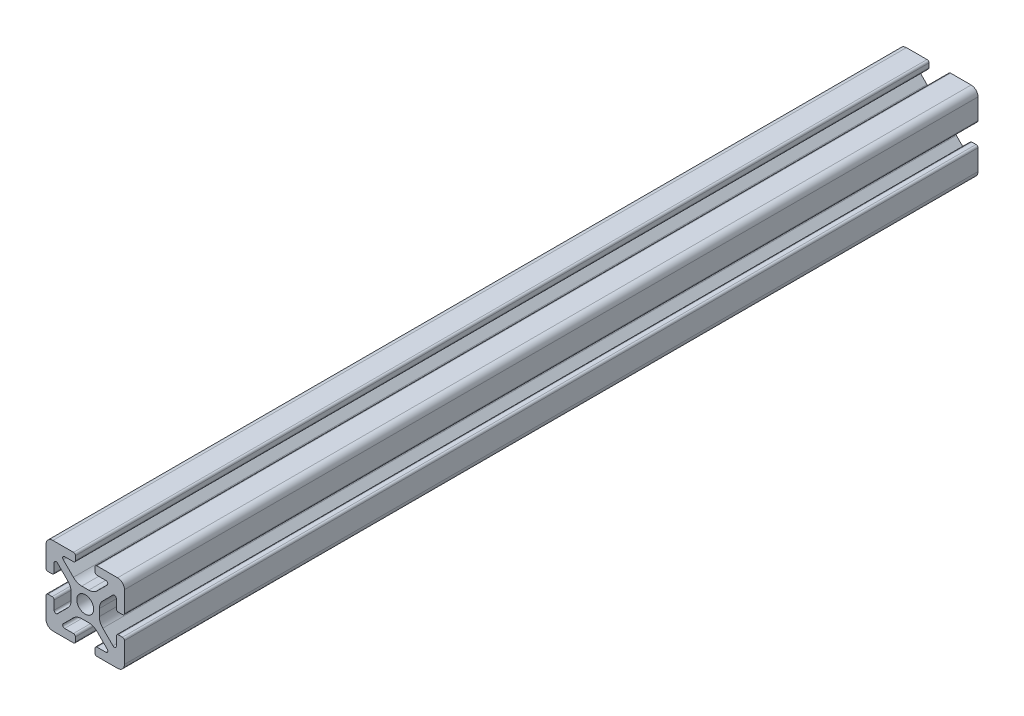
SolidWorks part; units mm, degrees
material "1060 Alloy"
ref_plane "Front Plane" through (0, 0, 0) normal (0, 0, 1) x (1, 0, 0)
ref_plane "Top Plane" through (0, 0, 0) normal (0, 1, 0) x (1, 0, 0)
ref_plane "Right Plane" through (0, 0, 0) normal (1, 0, 0) x (0, 0, -1)
sketch "Sketch2" plane through (0, 0, 0) normal (0, 0, 1) x (1, 0, 0)
  line L0 (0, 10) -> (0, -10) construction
  line L1 (-10, 0) -> (10, 0) construction
  line L2 (2.5, -10) -> (10, -10)
  line L3 (10, -10) -> (10, -2.5)
  line L4 (2.5, -10) -> (2.5, -7.9246)
  line L5 (2.5, -7.9246) -> (6.4571, -7.9246)
  line L6 (6.4571, -7.9246) -> (2.1325, -3.6)
  line L7 (0, 0) -> (10, -10) construction
  line L8 (10, -2.5) -> (7.9246, -2.5)
  line L9 (7.9246, -2.5) -> (7.9246, -6.4571)
  line L10 (7.9246, -6.4571) -> (3.6, -2.1325)
  line L11 (5.7623, -4.2948) -> (4.2948, -5.7623) construction
  circle A0 centre (0, 0) radius 2.15
  arc A1 (5.25, -7.9246) -> (5.6036, -7.0711) centre (5.25, -7.4246) ccw construction
  point P8 (0, -3.6)
  point P16 (5.0286, -5.0286)
  dimension "Center Hole Diameter" = 4.3
  dimension "D3" = 0.5
  dimension "Rail Height" = 20
  dimension "Rail Width" = 20
  dimension "T-Slot Width" = 5
  dimension "Slot Depth" = 6.4
  dimension "Slot Inner Width" = 11.5
sketch "Sketch3" plane through (0, 0, 0) normal (1, 0, 0) x (0, 0, -1)
  line L0 (-110, -10) -> (110, -10) construction
  line L1 (-84.6, 0) -> (84.6, 0) construction
  line L2 (0, 10) -> (0, -10) construction
  line L3 (0, 10) -> (0, -10) construction
  point P6 (-84.6, 0)
  point P8 (84.6, 0)
  dimension "Length" = 220
  dimension "D1" = 25.4
sketch "Sketch4" plane through (0, 0, 0) normal (0, 0, 1) x (1, 0, 0)
  line L0 (3, -10) -> (8.25, -10)
  line L1 (2.5, -10) -> (10, -10) construction
  line L2 (2.5, -10) -> (2.5, -7.9246) construction
  line L3 (2.5, -7.9246) -> (6.4571, -7.9246) construction
  line L4 (2.5, -8.4246) -> (2.5, -9.5)
  line L5 (3, -7.9246) -> (5.25, -7.9246)
  line L6 (0, -3.6) -> (0.8898, -3.6)
  line L7 (6.4571, -7.9246) -> (2.1325, -3.6) construction
  line L8 (3.0112, -4.4787) -> (5.6036, -7.0711)
  line L9 (10, -10) -> (10, -2.5) construction
  line L10 (7.9246, -6.4571) -> (3.6, -2.1325) construction
  line L11 (7.9246, -2.5) -> (7.9246, -6.4571) construction
  line L12 (7.9246, -5.25) -> (7.9246, -3)
  line L13 (10, -2.5) -> (7.9246, -2.5) construction
  line L14 (8.4246, -2.5) -> (9.5, -2.5)
  line L15 (10, -3) -> (10, -8.25)
  line L16 (7.0711, -5.6036) -> (4.4787, -3.0112)
  line L17 (3.6, 0) -> (3.6, -0.8898)
  line L18 (-10, 0) -> (10, 0) construction
  line L19 (0, -3.6) -> (0, -2.15)
  line L20 (0, 10) -> (0, -10) construction
  line L21 (3.6, 0) -> (2.15, 0)
  arc A0 (2.5, -9.5) -> (3, -10) centre (3, -9.5) ccw
  arc A1 (5.25, -7.9246) -> (5.6036, -7.0711) centre (5.25, -7.4246) ccw construction
  arc A2 (2.5, -8.4246) -> (3, -7.9246) centre (3, -8.4246) cw
  arc A3 (5.25, -7.9246) -> (5.6036, -7.0711) centre (5.25, -7.4246) ccw
  arc A4 (0.8898, -3.6) -> (3.0112, -4.4787) centre (0.8898, -6.6) cw
  arc A5 (8.25, -10) -> (10, -8.25) centre (8.25, -8.25) ccw
  arc A6 (7.0711, -5.6036) -> (7.9246, -5.25) centre (7.4246, -5.25) ccw
  arc A7 (7.9246, -3) -> (8.4246, -2.5) centre (8.4246, -3) cw
  arc A8 (9.5, -2.5) -> (10, -3) centre (9.5, -3) cw
  arc A9 (4.4787, -3.0112) -> (3.6, -0.8898) centre (6.6, -0.8898) cw
  circle A10 centre (0, 0) radius 2.15 construction
  arc A11 (0, -2.15) -> (2.15, 0) centre (0, 0) ccw
  dimension "D1" = 1.75
  dimension "D2" = 3
extrude "Boss-Extrude1" add sketch "Sketch4" along normal mid plane 220
mirror "Mirror1" about plane through (0, 0, 0) normal (1, 0, 0) of bodies 134
mirror "Mirror2" about plane through (0, 0, 0) normal (0, 1, 0) of bodies 135
sketch "Sketch5" plane through (0, 0, 110) normal (0, 0, 1) x (1, 0, 0)
  line L1 (-13.9539, 12.3566) -> (13.8334, 12.3566)
  line L2 (-13.9539, 12.3566) -> (-13.9539, -13.6827)
  line L3 (-13.9539, -13.6827) -> (13.8334, -13.6827)
  line L4 (13.8334, 12.3566) -> (13.8334, -13.6827)
extrude "Cut-Extrude1" cut sketch "Sketch5" against normal blind 2.4
equation "\"D3@Sketch2\"=\"T-Slot Width@Sketch2\"*0.1"
equation "\"D1@Sketch4\"=\"D3@Sketch2\"*3.5"
equation "\"D2@Sketch4\"=\"D3@Sketch2\"*6"
equation "\"D1@Boss-Extrude1\"=\"Length@Sketch3\""
